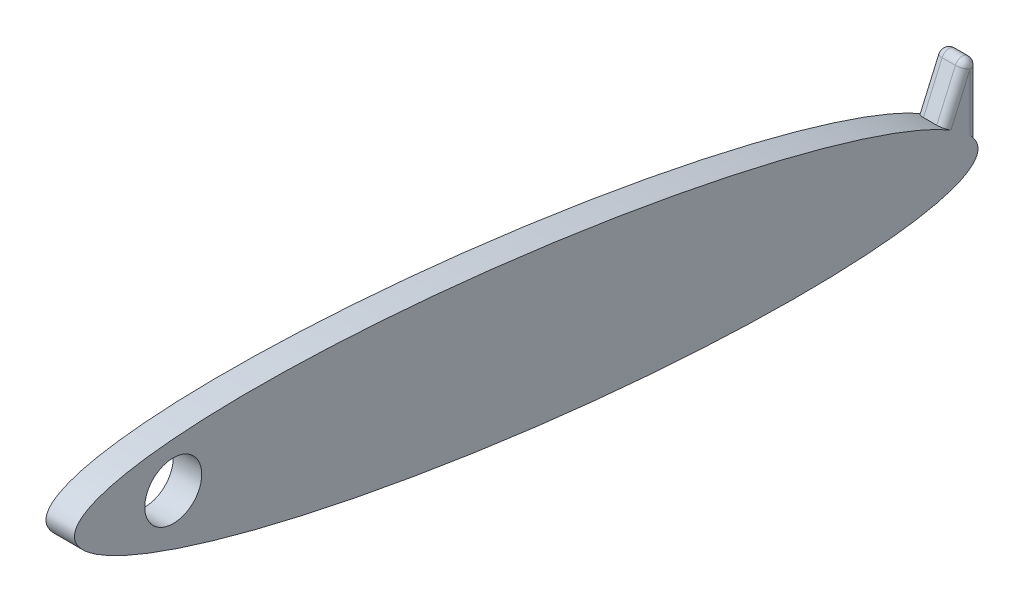
SolidWorks part; units mm, degrees
ref_plane "Front Plane" through (0, 0, 0) normal (0, 0, 1) x (1, 0, 0)
ref_plane "Top Plane" through (0, 0, 0) normal (0, 1, 0) x (1, 0, 0)
ref_plane "Right Plane" through (0, 0, 0) normal (1, 0, 0) x (0, 0, -1)
sketch "Sketch1" plane through (0, 0, 0) normal (1, 0, 0) x (0, 0, -1)
  ellipse E0 centre (0, 0) end of major axis (75.545, -9.9694) minor radius 12.7
extrude "Boss-Extrude1" add sketch "Sketch1" along normal blind 4.7625
sketch "Sketch2" plane through (0, 0, 0) normal (1, 0, 0) x (0, 0, -1)
  line L0 (67.587, -9.4826) -> (75.4823, -9.4826)
  line L1 (75.4823, -9.4826) -> (75.4823, 8.5625)
  line L2 (75.4823, 8.5625) -> (67.587, -9.4826)
extrude "Boss-Extrude2" add sketch "Sketch2" along normal blind 4.7625 separate body
fillet "Fillet3" radius 1.27 4 edges at (4.7625, -0.4601, -75.4823) (2.3813, 8.5625, -75.4823) (0, -0.4601, -71.5346) (4.7625, -0.4601, -71.5346)
fillet "Fillet4" radius 1.27 2 edges at (0.372, 3.6742, -73.7495) (0, -3.4955, -75.4823)
sketch "Sketch3" plane through (0, 0, 0) normal (1, 0, 0) x (0, 0, -1)
  circle A0 centre (-59.0406, 8.0659) radius 4.7625
extrude "Cut-Extrude3" cut sketch "Sketch3" against normal through all and the other way through all contours A0
combine bodies "Combine1" operation type add bodies to combine 106 105
